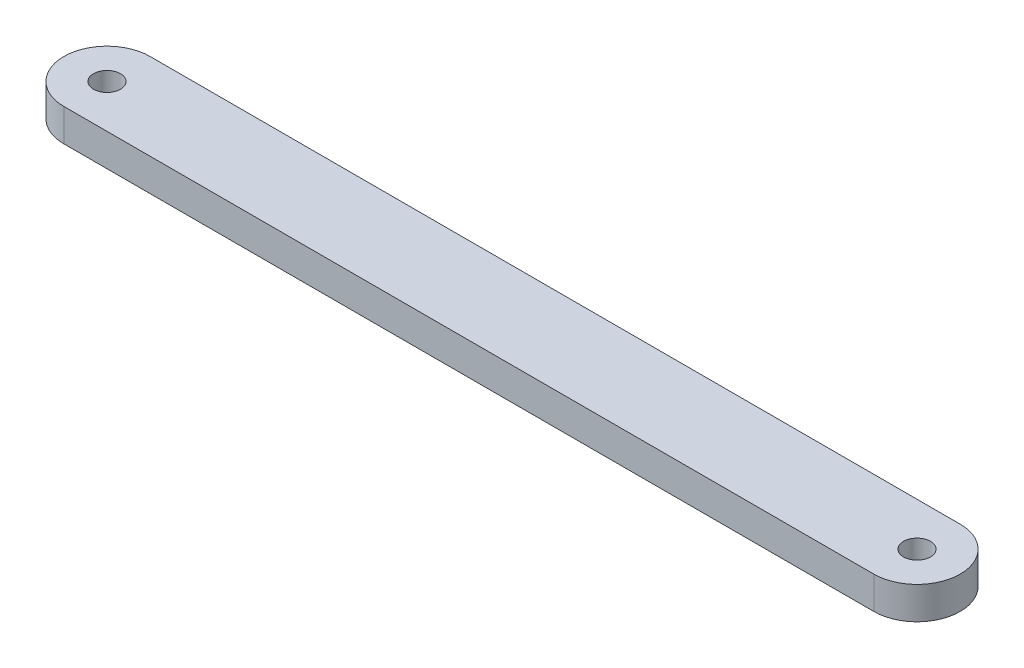
SolidWorks part; units mm, degrees
ref_plane "Front Plane" through (0, 0, 0) normal (0, 0, 1) x (1, 0, 0)
ref_plane "Top Plane" through (0, 0, 0) normal (0, 1, 0) x (1, 0, 0)
ref_plane "Right Plane" through (0, 0, 0) normal (1, 0, 0) x (0, 0, -1)
sketch "Sketch2" plane through (0, 0, 0) normal (0, 1, 0) x (1, 0, 0)
  line L0 (75, 0) -> (-75, 0) construction
  line L1 (75, -8) -> (-75, -8)
  line L2 (75, 8) -> (-75, 8)
  arc A0 (75, -8) -> (75, 8) centre (75, 0) ccw
  arc A1 (-75, 8) -> (-75, -8) centre (-75, 0) ccw
  circle A2 centre (75, 0) radius 2.5
  circle A3 centre (-75, 0) radius 2.5
  point P3 (0, 0)
  dimension "D2" = 8
  dimension "D3" = 5
  dimension "D1" = 150
extrude "Boss-Extrude1" add sketch "Sketch2" along normal blind 6
